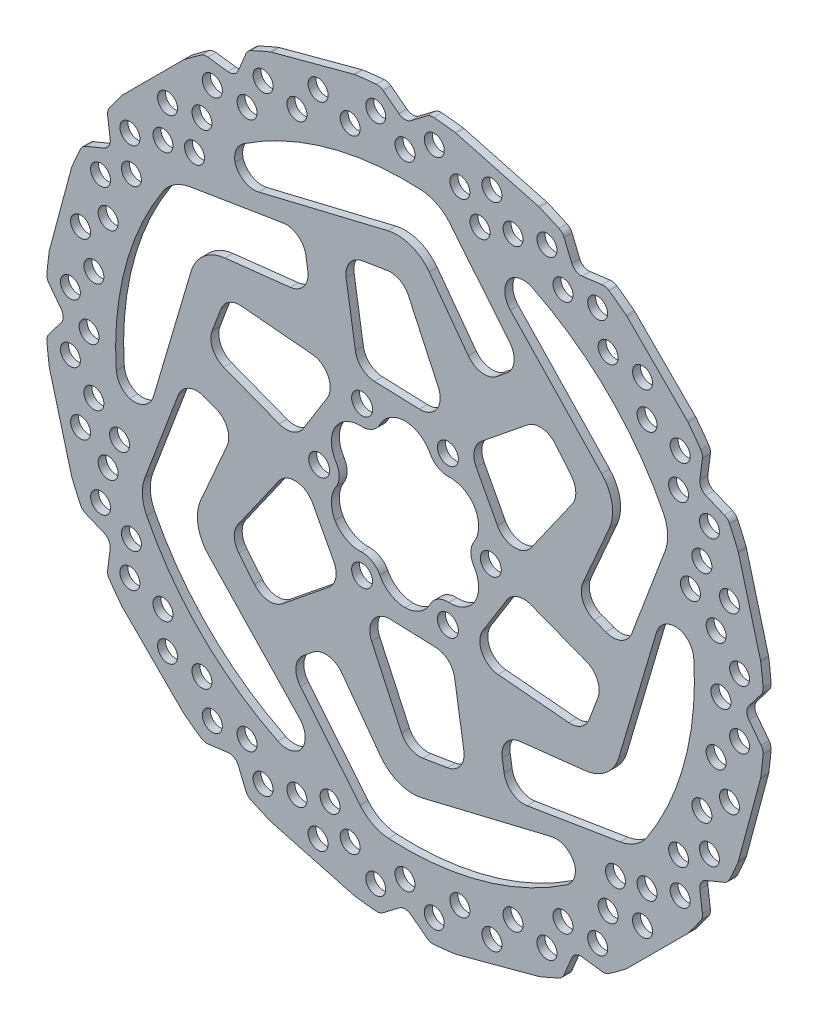
SolidWorks part; units mm, degrees
ref_plane "Front Plane" through (0, 0, 0) normal (0, 0, 1) x (1, 0, 0)
ref_plane "Top Plane" through (0, 0, 0) normal (0, 1, 0) x (1, 0, 0)
ref_plane "Right Plane" through (0, 0, 0) normal (1, 0, 0) x (0, 0, -1)
sketch "Sketch3" plane through (0, 0, 0) normal (0, 0, 1) x (1, 0, 0)
  circle A0 centre (0, 0) radius 90
  dimension "D1" = 180
extrude "Boss-Extrude1" add sketch "Sketch3" along normal blind 1 and the other way blind 1
sketch "Sketch4" plane through (0, 0, 0) normal (0, 0, 1) x (1, 0, 0)
  line L0 (0, 0) -> (21.5, 0) construction
  circle A0 centre (0, 0) radius 20.25
  circle A2 centre (21.5, 0) radius 2.625
  circle A3 centre (21.5, 0) radius 5
  circle A4 centre (10.75, -18.6195) radius 5
  circle A5 centre (10.75, -18.6195) radius 2.625
  circle A6 centre (-10.75, -18.6195) radius 5
  circle A7 centre (-10.75, -18.6195) radius 2.625
  circle A8 centre (-21.5, 0) radius 5
  circle A9 centre (-21.5, 0) radius 2.625
  circle A10 centre (-10.75, 18.6195) radius 5
  circle A11 centre (-10.75, 18.6195) radius 2.625
  circle A12 centre (10.75, 18.6195) radius 5
  circle A13 centre (10.75, 18.6195) radius 2.625
  point P7 (0, 0)
  point P8 (0, 0)
  point P24 (0, 0)
  dimension "D1" = 40.5
  dimension "D2" = 5.25
  dimension "D4" = 10
  dimension "D5" = 6
  dimension "D3" = 21.5
extrude "Cut-Extrude1" cut sketch "Sketch4" against normal through all both and the other way through all contours A12 A0 A10 A8 A6 A4 A3 | A0 A9 | A0 A9 | A0 A11 | A0 A11 | A0 A13 | A0 A13 | L0 A2 A0 | A0 A2 | A2 L0 A0 | A0 A5 | A0 A5 | A0 A7 | A0 A7 region at (16.9126, -3.1505, 0) region at (19.6618, 0.8708, 0) region at (19.6618, -0.8708, 0) region at (21.9589, 0, 0) region at (9.8309, 17.0276, 0) region at (10.9795, 19.017, 0) region at (10.9795, -19.017, 0) region at (9.8309, -17.0276, 0) region at (-9.8309, 17.0276, 0) region at (-10.9795, 19.017, 0) region at (-10.9795, -19.017, 0) region at (-9.8309, -17.0276, 0) region at (-19.6618, 0, 0) region at (-21.9589, 0, 0)
fillet "Fillet1" radius 7.25 12 edges at (19.7049, -4.6667, 0) (13.8939, -14.7316, 0) (5.811, -19.3983, 0) (-5.811, -19.3983, 0) (-13.8939, -14.7316, 0) (-19.7049, -4.6667, 0) (-19.7049, 4.6667, 0) (-13.8939, 14.7316, 0) (5.811, 19.3983, 0) (13.8939, 14.7316, 0) (19.7049, 4.6667, 0) (-5.811, 19.3983, 0)
sketch "Sketch5" plane through (0, 0, 0) normal (0, 0, 1) x (1, 0, 0)
  line L0 (-15.5226, 48.8704) -> (-11.7824, 25.1636)
  line L1 (-11.7824, 25.1636) -> (11.7824, 24.3325)
  line L2 (11.7824, 24.3325) -> (-0.7191, 51.2899)
  line L3 (-0.7191, 51.2899) -> (-15.5226, 48.8704)
  line L4 (-58.0446, 43.4404) -> (-25.6256, 48.739)
  line L5 (-25.6256, 48.739) -> (-23.5304, 35.4586)
  line L6 (-23.5304, 35.4586) -> (-51.7044, 32.3175)
  line L7 (-51.7044, 32.3175) -> (-64.4193, -10.7077)
  line L8 (-64.4193, -10.7077) -> (-72.004, -8.4662)
  line L9 (0, 20.2481) -> (0, 24.7481) construction
  line L10 (-11.1591, 21.2125) -> (-15.5226, 48.8704) construction
  line L11 (9.8805, 21.0964) -> (-0.7191, 51.2899) construction
  line L12 (-10.75, 18.6195) -> (-11.1591, 21.2125) construction
  line L13 (10.75, 18.6195) -> (9.8805, 21.0964) construction
  line L14 (-10.75, 18.6195) -> (-11.1591, 21.2125) construction
  line L15 (-11.1591, 21.2125) -> (-11.7824, 25.1636) construction
  line L16 (-23.5304, 35.4586) -> (-13.6525, 37.017) construction
  line L17 (-58.0619, 10.8049) -> (-71.0084, 14.6309) construction
  line L18 (-51.7044, 32.3175) -> (-53.64, 44.1603)
  line L19 (-58.0619, 10.8049) -> (-24.0174, 0.7439) construction
  line L20 (-24.0174, 0.7439) -> (-21.5, 0) construction
  circle A0 centre (0, 0) radius 72.5
  circle A1 centre (-10.75, 18.6195) radius 2.625 construction
  circle A2 centre (10.75, 18.6195) radius 2.625 construction
  circle A3 centre (-21.5, 0) radius 2.625 construction
  point P30 (-64.2723, -16.2684)
  point P37 (-53.096, 33.1033)
  point P38 (-57.1598, 44.9461)
  point P39 (-25.7815, 49.7268)
  point P40 (-24.0602, 35.4586)
  point P41 (-53.096, 33.1033)
  point P42 (-71.6072, -14.7491)
  point P43 (-64.2723, -16.2684)
  dimension "D8" = 145
  dimension "D1" = 26.5
  dimension "D2" = 4.5
  dimension "D3" = 15
  dimension "D4" = 24
  dimension "D5" = 28
  dimension "D6" = 32
  dimension "D7" = 4
  dimension "D9" = 10
  dimension "D10" = 13.5
  dimension "D11" = 12
  dimension "D12" = 1.5
  dimension "D13" = 35.5
extrude "Cut-Extrude2" cut sketch "Sketch5" against normal through all both and the other way through all contours L2 L3 L0 L1 | L18 L6 L5 L4 | L4 A0 L8 L7 L18 region at (-3.5666, 36.5851, 0) region at (-62.8189, 16.8148, 0) region at (-38.3594, 40.208, 0)
fillet "Fillet2" radius 5 8 edges at (-11.7824, 25.1636, 0) (-0.7191, 51.2899, 0) (11.7824, 24.3325, 0) (-15.5226, 48.8704, 0) (-64.4193, -10.7077, 0) (-72.004, -8.4662, 0) (-23.5304, 35.4586, 0) (-25.6256, 48.739, 0)
fillet "Fillet3" radius 10 2 edges at (-58.0446, 43.4404, 0) (-51.7044, 32.3175, 0)
pattern_circular "CirPattern1" count 6 over 360 about axis through (0, 0, 1) along (0, 0, 1) of "Cut-Extrude2", "Fillet3", "Fillet2"
sketch "Sketch6" plane through (0, 0, 0) normal (0, 0, 1) x (1, 0, 0)
  line L0 (0, 0) -> (92.5, 0) construction
  line L1 (-46.25, 80.1073) -> (-80.1073, 46.25)
  line L2 (-80.1073, 46.25) -> (-92.5, 0)
  line L3 (-92.5, 0) -> (-80.1073, -46.25)
  line L4 (-80.1073, -46.25) -> (-46.25, -80.1073)
  line L5 (-46.25, -80.1073) -> (0, -92.5)
  line L6 (0, -92.5) -> (46.25, -80.1073)
  line L7 (46.25, -80.1073) -> (80.1073, -46.25)
  line L8 (80.1073, -46.25) -> (92.5, 0)
  line L9 (92.5, 0) -> (80.1073, 46.25)
  line L10 (80.1073, 46.25) -> (46.25, 80.1073)
  line L11 (46.25, 80.1073) -> (0, 92.5)
  line L12 (0, 92.5) -> (-46.25, 80.1073)
  circle A0 centre (0, 0) radius 89.3481 construction
  circle A1 centre (0, 0) radius 90
  circle A2 centre (0, 0) radius 90 construction
  point P18 (94.9942, 0)
  point P19 (102.4379, 0)
  dimension "D1" = 92.5
extrude "Cut-Extrude3" cut sketch "Sketch6" against normal through all both and the other way through all contours L9 A1 | L8 A1 | L7 A1 | L6 A1 | L5 A1 | L4 A1 | L3 A1 | L2 A1 | L1 A1 | L12 A1 | L11 A1 | L10 A1 region at (-63.3631, 63.3631, 0) region at (-23.1925, 86.5556, 0) region at (-86.5556, 23.1925, 0) region at (23.1925, 86.5556, 0) region at (-86.5556, -23.1925, 0) region at (63.3631, 63.3631, 0) region at (-63.3631, -63.3631, 0) region at (86.5556, 23.1925, 0) region at (-23.1925, -86.5556, 0) region at (86.5556, -23.1925, 0) region at (23.1925, -86.5556, 0) region at (63.3631, -63.3631, 0)
sketch "Sketch7" plane through (0, 0, 0) normal (0, 0, 1) x (1, 0, 0)
  line L0 (89.7827, -6.25) -> (85, 0)
  line L1 (85, 0) -> (89.7827, 6.25)
  line L2 (0, 0) -> (85, 0) construction
  line L3 (85, 0) -> (90, 0) construction
  line L4 (74.6291, -50.304) -> (73.6122, -42.5)
  line L5 (73.6122, -42.5) -> (80.8791, -39.4787)
  line L6 (39.4787, -80.8791) -> (42.5, -73.6122)
  line L7 (42.5, -73.6122) -> (50.304, -74.6291)
  line L8 (-6.25, -89.7827) -> (0, -85)
  line L9 (0, -85) -> (6.25, -89.7827)
  line L10 (-50.304, -74.6291) -> (-42.5, -73.6122)
  line L11 (-42.5, -73.6122) -> (-39.4787, -80.8791)
  line L12 (-80.8791, -39.4787) -> (-73.6122, -42.5)
  line L13 (-73.6122, -42.5) -> (-74.6291, -50.304)
  line L14 (-89.7827, 6.25) -> (-85, 0)
  line L15 (-85, 0) -> (-89.7827, -6.25)
  line L16 (-74.6291, 50.304) -> (-73.6122, 42.5)
  line L17 (-73.6122, 42.5) -> (-80.8791, 39.4787)
  line L18 (-39.4787, 80.8791) -> (-42.5, 73.6122)
  line L19 (-42.5, 73.6122) -> (-50.304, 74.6291)
  line L20 (6.25, 89.7827) -> (0, 85)
  line L21 (0, 85) -> (-6.25, 89.7827)
  line L22 (50.304, 74.6291) -> (42.5, 73.6122)
  line L23 (42.5, 73.6122) -> (39.4787, 80.8791)
  line L24 (80.8791, 39.4787) -> (73.6122, 42.5)
  line L25 (73.6122, 42.5) -> (74.6291, 50.304)
  circle A0 centre (0, 0) radius 90
  point P6 (0, 0)
  point P9 (0, 0)
  point P44 (0, 0)
  dimension "D4" = 180
  dimension "D1" = 5
  dimension "D2" = 12.5
  dimension "D3" = 12
extrude "Cut-Extrude4" cut sketch "Sketch7" against normal through all both and the other way through all contours L0 A0 L1 | L24 A0 L25 | L22 A0 L23 | L18 A0 L19 | L16 A0 L17 | L14 A0 L15 | L12 A0 L13 | L6 A0 L7 | L8 A0 L9 | L10 A0 L11 | L4 A0 L5 | L20 A0 L21 region at (88.2845, 0, 0) region at (76.4566, -44.1423, 0) region at (76.4566, 44.1423, 0) region at (44.1423, -76.4566, 0) region at (44.1423, 76.4566, 0) region at (0, -88.2845, 0) region at (0, 88.2845, 0) region at (-44.1423, -76.4566, 0) region at (-44.1423, 76.4566, 0) region at (-76.4566, -44.1423, 0) region at (-76.4566, 44.1423, 0) region at (-88.2845, 0, 0)
fillet "Fillet4" radius 2.5 60 edges at (85, 0, 0) (89.7827, 6.25, 0) (89.1022, 12.6809, 0) (83.5052, 33.5691, 0) (80.8791, 39.4787, 0) (73.6122, 42.5, 0) (74.6291, 50.304, 0) (70.8243, 55.5331, 0) (55.5331, 70.8243, 0) (50.304, 74.6291, 0) (42.5, 73.6122, 0) (39.4787, 80.8791, 0) (33.5691, 83.5052, 0) (12.6809, 89.1022, 0) (0, 85, 0) (-6.25, 89.7827, 0) (-12.6809, 89.1022, 0) (-33.5691, 83.5052, 0) (-39.4787, 80.8791, 0) (-42.5, 73.6122, 0) (-50.304, 74.6291, 0) (-55.5331, 70.8243, 0) (-70.8243, 55.5331, 0) (-74.6291, 50.304, 0) (-73.6122, 42.5, 0) (-80.8791, 39.4787, 0) (-83.5052, 33.5691, 0) (-89.1022, 12.6809, 0) (-89.7827, 6.25, 0) (-85, 0, 0) (-89.7827, -6.25, 0) (-89.1022, -12.6809, 0) (-83.5052, -33.5691, 0) (-80.8791, -39.4787, 0) (-73.6122, -42.5, 0) (-74.6291, -50.304, 0) (-70.8243, -55.5331, 0) (-55.5331, -70.8243, 0) (-50.304, -74.6291, 0) (-42.5, -73.6122, 0) (-39.4787, -80.8791, 0) (-33.5691, -83.5052, 0) (-12.6809, -89.1022, 0) (-6.25, -89.7827, 0) (0, -85, 0) (6.25, -89.7827, 0) (12.6809, -89.1022, 0) (33.5691, -83.5052, 0) (39.4787, -80.8791, 0) (42.5, -73.6122, 0) (50.304, -74.6291, 0) (55.5331, -70.8243, 0) (70.8243, -55.5331, 0) (74.6291, -50.304, 0) (73.6122, -42.5, 0) (80.8791, -39.4787, 0) (83.5052, -33.5691, 0) (89.1022, -12.6809, 0) (89.7827, -6.25, 0) (6.25, 89.7827, 0)
sketch "Sketch8" plane through (0, 0, 0) normal (0, 0, 1) x (1, 0, 0)
  line L0 (79.148, 0) -> (81.648, 0) construction
  line L1 (81.648, 0) -> (85.648, 0) construction
  line L2 (71.5109, 19.599) -> (77.9456, 13.7439) construction
  line L3 (74.3748, 27.0702) -> (81.2807, 21.7791) construction
  line L4 (79.148, 0) -> (83.8278, -7.334) construction
  line L5 (83.8278, -7.334) -> (77.9456, -13.7439) construction
  line L6 (77.9456, -13.7439) -> (81.2807, -21.7791) construction
  line L7 (81.2807, -21.7791) -> (74.3748, -27.0702) construction
  line L8 (74.3748, -27.0702) -> (76.264, -35.5625) construction
  line L9 (76.264, -35.5625) -> (68.5442, -39.574) construction
  line L10 (68.5442, -39.574) -> (74.1733, -42.824) construction
  line L11 (73.8594, -44.3971) -> (75.3787, -41.7656) construction
  line L12 (74.1733, -42.824) -> (74.619, -43.0813) construction
  line L13 (79.148, 0) -> (83.8278, 7.334) construction
  line L14 (83.8278, 7.334) -> (77.9456, 13.7439) construction
  line L15 (77.9456, 13.7439) -> (81.2807, 21.7791) construction
  line L16 (74.3748, 27.0702) -> (76.264, 35.5625) construction
  line L17 (76.264, 35.5625) -> (68.5442, 39.574) construction
  circle A0 centre (79.148, 0) radius 2.5
  circle A1 centre (83.8278, -7.334) radius 2.5
  circle A2 centre (77.9456, -13.7439) radius 2.5
  circle A3 centre (81.2807, -21.7791) radius 2.5
  circle A4 centre (74.3748, -27.0702) radius 2.5
  circle A5 centre (76.264, -35.5625) radius 2.5
  circle A6 centre (83.8278, 7.334) radius 2.5
  circle A7 centre (77.9456, 13.7439) radius 2.5
  circle A8 centre (81.2807, 21.7791) radius 2.5
  circle A9 centre (74.3748, 27.0702) radius 2.5
  circle A10 centre (71.5109, 19.599) radius 2.5
  circle A11 centre (76.264, 35.5625) radius 2.5
  circle A12 centre (68.5442, 39.574) radius 2.5
  arc A13 (86.1626, 1.5193) -> (86.1626, -1.5193) centre (88.148, 0) ccw construction
  circle A14 centre (0, 0) radius 79.148 construction
  circle A15 centre (0, 0) radius 84.148 construction
  circle A16 centre (0, 0) radius 74.148 construction
  arc A17 (75.3787, -41.7656) -> (73.8594, -44.3971) centre (76.3384, -44.074) ccw construction
  dimension "D1" = 5
  dimension "D2" = 5
  dimension "D3" = 4
  dimension "D4" = 5
extrude "Cut-Extrude5" cut sketch "Sketch8" against normal through all both and the other way through all
pattern_circular "CirPattern2" count 6 over 360 about axis through (0, 0, 1) along (0, 0, 1) of "Cut-Extrude5"
